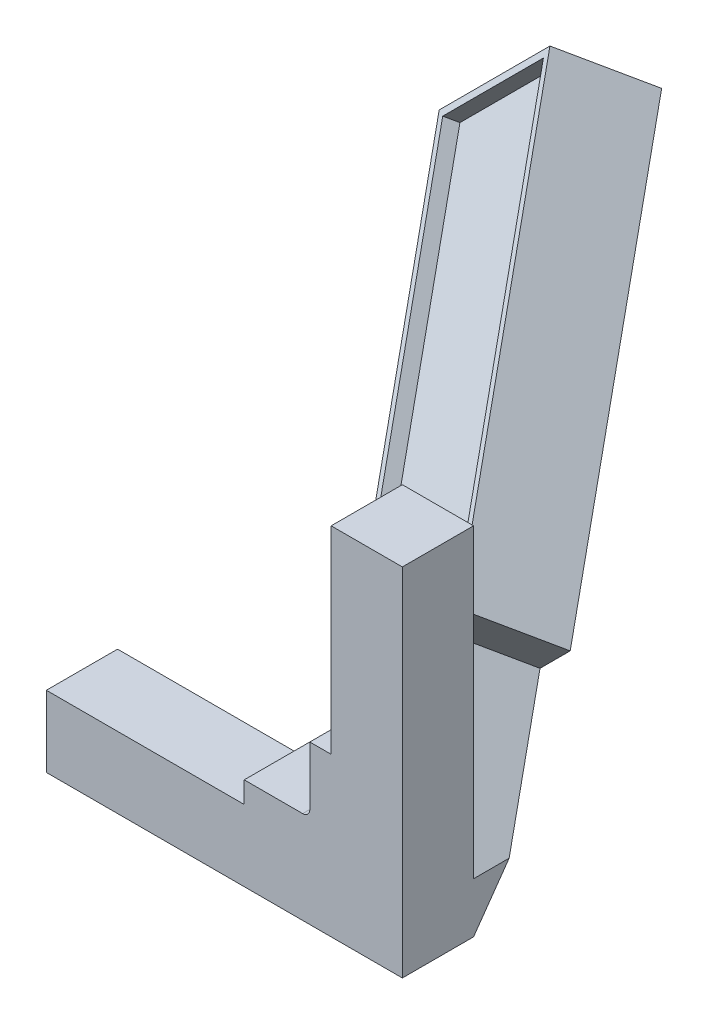
SolidWorks part; units mm, degrees
ref_plane "Front Plane" through (0, 0, 0) normal (0, 0, 1) x (1, 0, 0)
ref_plane "Top Plane" through (0, 0, 0) normal (0, 1, 0) x (1, 0, 0)
ref_plane "Right Plane" through (0, 0, 0) normal (1, 0, 0) x (0, 0, -1)
sketch "Sketch1" plane through (0, 0, 0) normal (0, 0, 1) x (1, 0, 0)
  line L0 (-13.8957, -26.1043) -> (13.8957, -26.1043)
  line L6 (26.1043, 13.8957) -> (36.1043, 13.8957)
  line L11 (26.1043, 13.8957) -> (26.1043, -13.8957)
  line L13 (23.1062, -23.1062) -> (36.1043, -36.1043) construction
  line L14 (26.1043, -13.8957) -> (23.1062, -13.8957)
  line L17 (13.8957, -26.1043) -> (13.8957, -23.1062)
  line L18 (23.1062, -17.3543) -> (26.1043, -17.3543)
  line L20 (26.1043, -17.3543) -> (26.1043, -26.1043)
  line L22 (36.1043, 13.8957) -> (36.1043, -36.1043)
  line L23 (26.1043, -26.1043) -> (17.3543, -26.1043)
  line L24 (17.3543, -26.1043) -> (17.3543, -23.1062)
  line L25 (23.1062, -13.8957) -> (23.1062, -23.1062)
  line L27 (23.1062, -23.1062) -> (13.8957, -23.1062)
  line L31 (-13.8957, -26.1043) -> (-13.8957, -36.1043)
  line L36 (36.1043, -36.1043) -> (-13.8957, -36.1043)
  point P10 (0, -26.1043)
  point P11 (26.1043, 0)
  dimension "D1" = 9.2105
  dimension "D2" = 10
  dimension "D3" = 8.75
  dimension "D4" = 50
  dimension "D6" = 2.9981
extrude "base" add sketch "Sketch1" along normal mid plane 10 contours L20 L13 L22 L6 L11 L14 L25 L18 | L13 L23 L24 L27 L17 L0 L31 L36 | L13 L27 L24 L23 | L25 L13 L20 L18 region at (8.8529, -31.1389, 0) region at (31.1389, -8.8529, 0) region at (21.0314, -24.7085, 0) region at (24.7085, -21.0314, 0)
ref_plane "arm plane" through (0, 0, 0) normal (-0.7071, -0.7071, 0) x (-0.7071, 0.7071, 0)
sketch "Sketch2" plane through (0, 0, 0) normal (-0.7071, -0.7071, 0) x (-0.7071, 0.7071, 0)
  line L0 (-51.0592, 5) -> (-31.2615, 24.7977)
  line L1 (-31.2615, 24.7977) -> (-22.0705, 15.6066)
  line L2 (-22.0705, 15.6066) -> (-32.6771, 5)
  line L3 (-51.0592, 5) -> (-32.6771, 5)
  line L5 (-51.0592, 5) -> (-15.7038, 5) construction
  line L6 (-32.6771, -5) -> (-32.6771, 5) construction
  line L7 (-51.0592, -5) -> (-51.0592, 5) construction
  point P3 (0, 0)
  point P7 (0, 0)
  point P10 (0, 0)
  point P13 (0, 0)
  dimension "D1" = 15
  dimension "D2" = 45
extrude "arm" add sketch "Sketch2" along normal mid plane 10
sketch "Sketch3" plane through (0, 0, 0) normal (0, 0, 1) x (1, 0, 0)
  line L0 (36.1043, -29.0332) -> (36.1043, -36.1043)
  line L1 (36.1043, 13.8957) -> (36.1043, -36.1043) construction
  line L2 (36.1043, -36.1043) -> (29.0332, -36.1043)
  line L3 (29.0332, -36.1043) -> (32.7809, -39.8519)
  line L4 (32.7809, -39.8519) -> (39.8519, -32.7809)
  line L5 (39.8519, -32.7809) -> (36.1043, -29.0332)
  line L6 (12.0706, -19.1417) -> (19.1417, -12.0706) construction
  line L7 (32.5687, -39.6398) -> (29.0332, -36.1043) construction
  line L8 (39.6398, -32.5687) -> (36.1043, -29.0332) construction
  point P11 (0, 0)
  point P12 (0, 0)
  point P17 (0, 0)
  point P21 (0, 0)
  dimension "D1" = 0.3
extrude "Cut-Extrude1" cut sketch "Sketch3" against normal through all
ref_plane "Plane2" through (0, 0, -5) normal (0, 0, -1) x (-1, 0, 0)
sketch "Sketch5" plane through (0, 0, -5) normal (0, 0, -1) x (-1, 0, 0)
  line L0 (-19.5706, -26.6417) -> (-16.0351, -23.1062)
  line L1 (-23.1062, -23.1062) -> (-13.8957, -23.1062) construction
  line L2 (-23.1062, -23.1062) -> (-13.8957, -23.1062) construction
  line L3 (-16.0351, -23.1062) -> (-23.1062, -23.1062)
  line L4 (-23.1062, -23.1062) -> (-23.1062, -16.0351)
  line L5 (-23.1062, -13.8957) -> (-23.1062, -23.1062) construction
  line L6 (-19.1417, -12.0706) -> (-25.6408, -18.5697) construction
  line L7 (-23.1062, -16.0351) -> (-26.6417, -19.5706)
  line L8 (-26.6417, -19.5706) -> (-26.6417, -26.6417)
  line L9 (-23.1062, -23.1062) -> (-36.1043, -36.1043) construction
  line L10 (-26.6417, -26.6417) -> (-19.5706, -26.6417)
  point P2 (0, 0)
  point P7 (0, 0)
  point P20 (-45.4231, -28.8008)
  dimension "D1" = 5
  dimension "D2" = 10
extrude "Boss-Extrude4" add sketch "Sketch5" along normal up to surface (5 mm away) contours L8 L10 L0 L3 L4 L7 | L7 L8 L10 L0 L3 L4 region at (23.1062, -26.4917, -5) up to face at (20.1062, -20.1062, -9.2426)
fillet "Fillet2" radius 1 1 edges at (23.1062, -23.1062, 0)
ref_plane "Plane3" through (13.3209, -13.3209, -18.8385) normal (-0.5, 0.5, 0.7071) x (0.866, 0.2887, 0.4082)
sketch "Sketch6" plane through (13.3209, -13.3209, -18.8385) normal (-0.5, 0.5, 0.7071) x (0.866, 0.2887, 0.4082)
  line L0 (-6.3426, -10.0828) -> (11.6203, 2.6189)
  line L1 (-1.4436, -6.6187) -> (6.7213, -0.8452) construction
  line L2 (-6.3426, -10.0828) -> (-42.1383, 40.54)
  line L3 (-42.1383, 40.54) -> (-24.1754, 53.2417)
  line L4 (-24.1754, 53.2417) -> (11.6203, 2.6189)
  line L5 (-24.1754, 53.2417) -> (-6.3426, -10.0828) construction
  line L6 (11.6203, 2.6189) -> (-42.1383, 40.54) construction
  line L7 (-40.7445, 40.3009) -> (-24.4145, 51.8479)
  line L8 (-24.4145, 51.8479) -> (10.2265, 2.8581)
  line L9 (10.2265, 2.8581) -> (-6.1035, -8.6889)
  line L10 (-6.1035, -8.6889) -> (-40.7445, 40.3009)
  line L11 (-24.4145, 51.8479) -> (-6.1035, -8.6889) construction
  line L12 (10.2265, 2.8581) -> (-40.7445, 40.3009) construction
  point P4 (2.6389, -3.7319)
  point P11 (-15.259, 21.5795)
  dimension "D1" = 22
  dimension "D2" = 62
  dimension "D3" = 60
  dimension "D4" = 20
extrude "Boss-Extrude5" add sketch "Sketch6" against normal up to surface (12.9981 mm away) contours L10 L9 L8 L7 | L4 L3 L2 L0 L9 L10 L7 L8 region at (-7.0846, -7.297, -37.5269) region at (0.1062, -0.1062, -37.5269) up to face at (29.0904, -29.0904, -14.9191)
extrude "Cut-Extrude2" cut sketch "Sketch6<3>" against normal blind 2 contours L10 L9 L8 L7 region at (0.1062, -0.1062, -37.5269)
sketch "Sketch6<3>" plane through (13.3209, -13.3209, -18.8385) normal (-0.5, 0.5, 0.7071) x (0.866, 0.2887, 0.4082) same geometry as "Sketch6"
